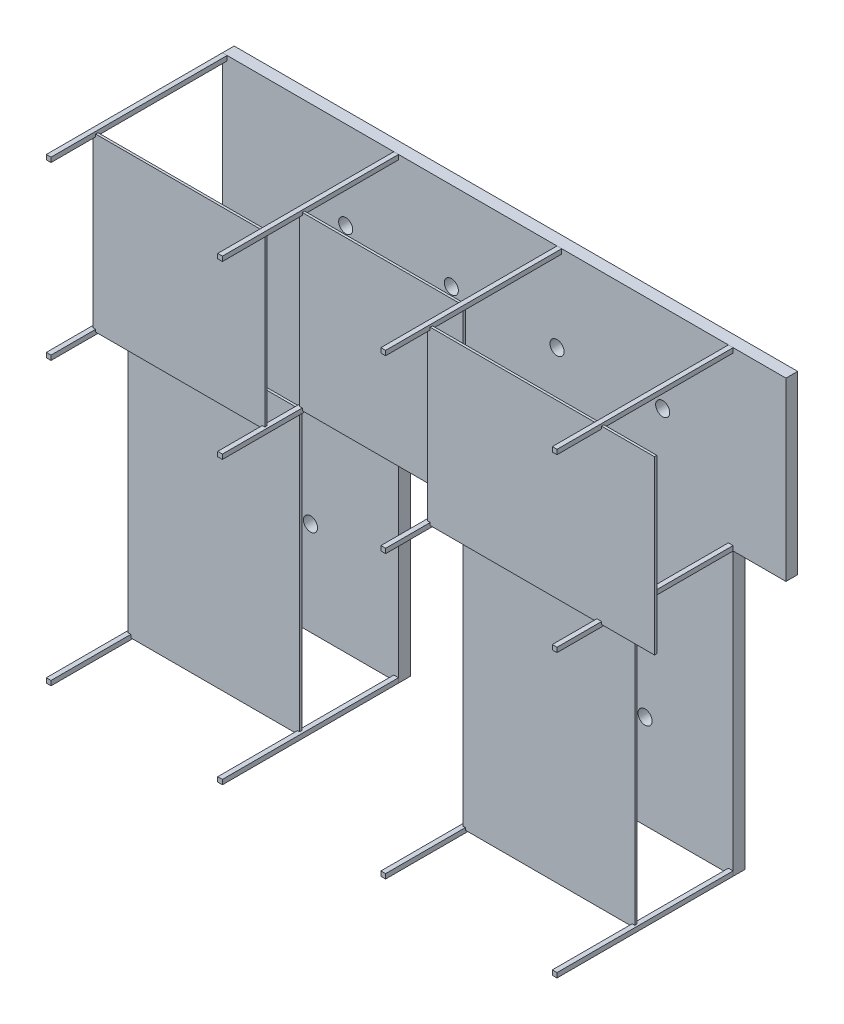
SolidWorks part; units mm, degrees
ref_plane "Front Plane" through (0, 0, 0) normal (0, 0, 1) x (1, 0, 0)
ref_plane "Top Plane" through (0, 0, 0) normal (0, 1, 0) x (1, 0, 0)
ref_plane "Right Plane" through (0, 0, 0) normal (1, 0, 0) x (0, 0, -1)
sketch "Sketch1" plane through (0, 0, 0) normal (0, 0, 1) x (1, 0, 0)
  line L0 (0, 0) -> (0, 3900)
  line L1 (0, 3900) -> (4800, 3900)
  line L2 (4800, 3900) -> (4800, 2400)
  line L3 (4800, 2400) -> (4350, 2400)
  line L4 (4350, 2400) -> (4350, 0)
  line L5 (4350, 0) -> (2850, 0)
  line L6 (2850, 0) -> (2850, 2400)
  line L7 (2850, 2400) -> (1500, 2400)
  line L8 (1500, 2400) -> (1500, 0)
  line L9 (1500, 0) -> (0, 0)
  circle A0 centre (1050, 3150) radius 60
  circle A1 centre (1950, 3150) radius 60
  circle A2 centre (2850, 3150) radius 60
  circle A3 centre (750, 800) radius 60
  circle A4 centre (3600, 800) radius 60
  circle A5 centre (3600, 1700) radius 60
  circle A6 centre (750, 1700) radius 60
  circle A7 centre (3750, 3150) radius 60
  circle A8 centre (750, 2600) radius 60
  circle A9 centre (3600, 2600) radius 60
  dimension "D8" = 1050
  dimension "D10" = 900
  dimension "D7" = 120
  dimension "D11" = 800
  dimension "D12" = 750
  dimension "D15" = 750
  dimension "D1" = 2400
  dimension "D2" = 3900
  dimension "D3" = 1350
  dimension "D4" = 1500
  dimension "D5" = 1500
  dimension "D6" = 4800
  dimension "D9" = 4
  dimension "D13" = 2
  dimension "D14" = 3
extrude "Boss-Extrude1" add sketch "Sketch1" along normal blind 100
sketch "Sketch2" plane through (0, 0, 100) normal (0, 0, 1) x (1, 0, 0)
  line L0 (2890, 2400) -> (2850, 2400)
  line L1 (0, 3900) -> (40, 3900)
  line L2 (0, 3900) -> (0, 3860)
  line L3 (0, 3860) -> (40, 3860)
  line L4 (40, 3900) -> (40, 3860)
  line L5 (0, 0) -> (40, 0)
  line L6 (0, 0) -> (0, 40)
  line L7 (0, 40) -> (40, 40)
  line L8 (40, 0) -> (40, 40)
  line L9 (1500, 0) -> (1460, 0)
  line L10 (1500, 0) -> (1500, 40)
  line L11 (1500, 40) -> (1460, 40)
  line L12 (1460, 0) -> (1460, 40)
  line L13 (1500, 2400) -> (1460, 2400)
  line L14 (1500, 2400) -> (1500, 2440)
  line L15 (1500, 2440) -> (1460, 2440)
  line L16 (1460, 2400) -> (1460, 2440)
  line L17 (2890, 2400) -> (2890, 2440)
  line L18 (2890, 2440) -> (2850, 2440)
  line L19 (2850, 2400) -> (2850, 2440)
  line L20 (1500, 3860) -> (1460, 3860)
  line L21 (4350, 0) -> (4310, 0)
  line L22 (4350, 0) -> (4350, 40)
  line L23 (4350, 40) -> (4310, 40)
  line L24 (4310, 0) -> (4310, 40)
  line L25 (2890, 0) -> (2850, 0)
  line L26 (2890, 0) -> (2890, 40)
  line L27 (2890, 40) -> (2850, 40)
  line L28 (2850, 0) -> (2850, 40)
  line L29 (4350, 2400) -> (4310, 2400)
  line L30 (4350, 2400) -> (4350, 2440)
  line L31 (4350, 2440) -> (4310, 2440)
  line L32 (4310, 2400) -> (4310, 2440)
  line L33 (4350, 3860) -> (4310, 3860)
  line L34 (4350, 3860) -> (4350, 3900)
  line L35 (4350, 3900) -> (4310, 3900)
  line L36 (4310, 3860) -> (4310, 3900)
  line L37 (2850, 0) -> (4350, 0) construction
  line L38 (2850, 2400) -> (2850, 0) construction
  line L39 (1500, 2400) -> (2850, 2400) construction
  line L40 (2890, 3860) -> (2850, 3860)
  line L41 (2890, 3860) -> (2890, 3900)
  line L42 (2890, 3900) -> (2850, 3900)
  line L43 (2850, 3860) -> (2850, 3900)
  line L44 (40, 2400) -> (0, 2400)
  line L45 (40, 2400) -> (40, 2440)
  line L46 (40, 2440) -> (0, 2440)
  line L47 (0, 2400) -> (0, 2440)
  line L48 (0, 3900) -> (0, 0) construction
  line L49 (4800, 3900) -> (0, 3900) construction
  line L50 (4350, 2400) -> (4800, 2400) construction
  line L51 (1500, 3860) -> (1500, 3900)
  line L52 (1500, 3900) -> (1460, 3900)
  line L53 (1460, 3860) -> (1460, 3900)
  line M7 (0, 0) -> (1500, 0)
  line M8 (1500, 0) -> (1500, 2400)
  line M9 (1500, 2400) -> (2850, 2400)
  line M10 (2850, 2400) -> (2850, 0)
  line M11 (2850, 0) -> (4350, 0)
  line M12 (4350, 0) -> (4350, 2400)
  line M15 (4800, 3900) -> (0, 3900)
  line M16 (0, 3900) -> (0, 0)
  dimension "D1" = 40
  dimension "D2" = 40
  dimension "D3" = 40
  dimension "D4" = 40
  dimension "D5" = 40
  dimension "D6" = 40
  dimension "D7" = 40
  dimension "D8" = 40
  dimension "D9" = 40
  dimension "D10" = 40
  dimension "D11" = 40
  dimension "D12" = 40
  dimension "D13" = 40
  dimension "D14" = 40
  dimension "D15" = 40
  dimension "D16" = 40
  dimension "D17" = 40
  dimension "D18" = 40
  dimension "D19" = 40
  dimension "D20" = 40
  dimension "D21" = 40
  dimension "D22" = 40
  dimension "D23" = 40
  dimension "D24" = 40
extrude "Boss-Extrude2" add sketch "Sketch2" along normal blind 1500 separate body contours L8 L7 M7 M16 | L16 L13 L14 L15 | L12 L11 M7 M8 | L24 L23 M11 M12 | L32 L29 L30 L31 | L36 L33 L34 M15 | L43 L40 L41 M15 | L19 L17 L18 M9 | L4 L3 M15 M16 | L45 L46 L44 M16 | L26 L27 M10 M11 | L53 L20 L51 M15 region at (4330, 2420, 100) region at (4330, 20, 100) region at (2870, 20, 100) region at (4330, 3880, 100) region at (2870, 3880, 100) region at (1480, 3880, 100) region at (20, 3880, 100) region at (20, 2420, 100) region at (20, 20, 100) region at (1480, 20, 100) region at (1480, 2420, 100) region at (2870, 2420, 100)
ref_plane "Plane2" through (0, 0, 900) normal (0, 0, 1) x (1, 0, 0)
sketch "Sketch3" plane through (0, 0, 900) normal (0, 0, 1) x (1, 0, 0)
  line L3 (2870.5919, 2420.0495) -> (1477.2184, 2420.0495)
  line L4 (2870.5919, 2420.0495) -> (2870.5919, 3882.092)
  line L7 (2870.5919, 3882.092) -> (1477.2184, 3882.092)
  line L8 (1477.2184, 2420.0495) -> (1477.2184, 3882.092)
  line L10 (1477.2184, 2420.0495) -> (17.0762, 2420.0495)
  line L13 (4332.9146, 2420.0495) -> (2870.5919, 2420.0495)
  line L14 (4332.9146, 2420.0495) -> (4332.9146, 20)
  line L15 (4332.9146, 20) -> (2870.5919, 20)
  line L16 (2870.5919, 2420.0495) -> (2870.5919, 20)
  line L21 (1477.2184, 2420.0495) -> (1477.2184, 13.9602)
  line L22 (1477.2184, 13.9602) -> (17.0762, 13.9602)
  line L23 (17.0762, 2420.0495) -> (17.0762, 13.9602)
ref_plane "Plane3" through (0, 0, 1200) normal (0, 0, 1) x (1, 0, 0)
sketch "Sketch5" plane through (0, 0, 1200) normal (0, 0, 1) x (1, 0, 0)
  line L0 (4800, 2400) -> (4800, 3900) construction
  line L1 (1481.2655, 2420) -> (16.3508, 2420)
  line L2 (1481.2655, 2420) -> (1481.2655, 3880.6022)
  line L3 (1481.2655, 3880.6022) -> (16.3508, 3880.6022)
  line L4 (16.3508, 2420) -> (16.3508, 3880.6022)
  line L7 (4800, 2417.6303) -> (2868.745, 2417.6303)
  line L8 (4800, 2417.6303) -> (4800, 3880.6022)
  line L9 (4800, 3880.6022) -> (2868.745, 3880.6022)
  line L10 (2868.745, 2417.6303) -> (2868.745, 3880.6022)
extrude "Boss-Extrude5" add sketch "Sketch5" along normal blind 20
extrude "Boss-Extrude6" add sketch "Sketch3" along normal blind 20 contours L10 L23 L22 L21 | L8 L3 L4 L7 | L16 L15 L14 L13 region at (747.1473, 1217.0049, 900) region at (2173.9051, 3151.0708, 900)
equation "\"A\"= 40"
equation "\"D9@Sketch2\"=\"A\""
equation "\"D10@Sketch2\"=\"A\""
equation "\"D11@Sketch2\"=\"A\""
equation "\"D12@Sketch2\"=\"A\""
equation "\"D6@Sketch2\"=\"A\""
equation "\"D5@Sketch2\"=\"A\""
equation "\"D4@Sketch2\"=\"A\""
equation "\"D3@Sketch2\"=\"A\""
equation "\"D8@Sketch2\"=\"A\""
equation "\"D7@Sketch2\"=\"A\""
equation "\"D2@Sketch2\"=\"A\""
equation "\"D1@Sketch2\"=\"A\""
equation "\"D13@Sketch2\"=\"A\""
equation "\"D14@Sketch2\"=\"A\""
equation "\"D15@Sketch2\"=\"A\""
equation "\"D16@Sketch2\"=\"A\""
equation "\"D17@Sketch2\"=\"A\""
equation "\"D18@Sketch2\"=\"A\""
equation "\"D\"= 120"
equation "\"D20@Sketch2\" = \"A\""
equation "\"D21@Sketch2\"=\"A\""
equation "\"D22@Sketch2\"=\"A\""
equation "\"D23@Sketch2\"=\"A\""
equation "\"b\"=750"
equation "\"D12@Sketch1\"=\"b\""
